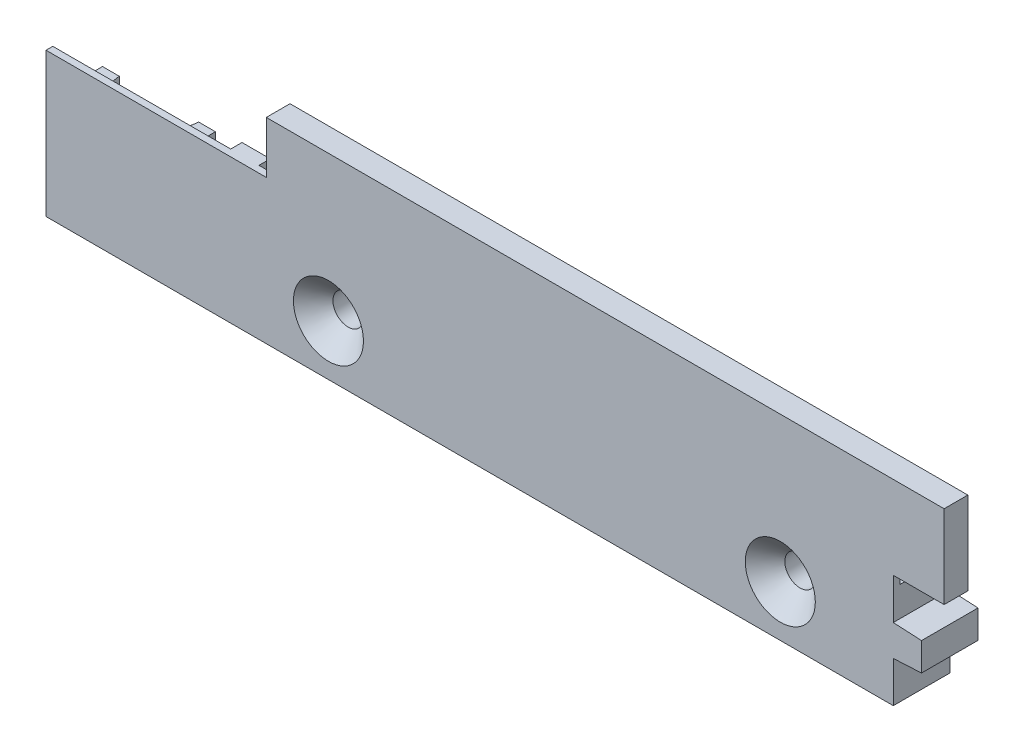
SolidWorks part; units mm, degrees
ref_plane "Front Plane" through (0, 0, 0) normal (0, 0, 1) x (1, 0, 0)
ref_plane "Top Plane" through (0, 0, 0) normal (0, 1, 0) x (1, 0, 0)
ref_plane "Right Plane" through (0, 0, 0) normal (1, 0, 0) x (0, 0, -1)
ref_axis "X-Axis" through (0, 0, 0) along (1, 0, 0)
ref_axis "Y-Axis" through (0, 42.2917, 0) along (0, -1, 0)
ref_axis "Z-Axis" through (0, 0, 55.0015) along (0, 0, -1)
sketch "Sketch1" plane through (0, 0, 0) normal (0, 0, 1) x (1, 0, 0)
  line L1 (-127.8191, -9.8629) -> (22.1809, -9.8629)
  line L2 (22.1809, -9.8629) -> (22.1809, -2.6129)
  line L3 (22.1809, -2.6129) -> (27.1809, -2.6129)
  line L4 (27.1809, -2.6129) -> (27.1809, 2.8871)
  line L5 (27.1809, 2.8871) -> (22.1809, 2.8871)
  line L6 (22.1809, 2.8871) -> (22.1809, 10.1371)
  line L7 (22.1809, 10.1371) -> (31.1809, 10.1371)
  line L8 (31.1809, 10.1371) -> (31.1809, 23.6371)
  line L10 (-127.8191, 15.6371) -> (-127.8191, -9.8629)
  line L12 (-88.8191, -25.8695) -> (-88.8191, 48.9262) construction
  line L13 (31.1809, 13.1371) -> (10.3885, 13.1371) construction
  line L14 (31.1809, 23.6371) -> (-88.8191, 23.6371) construction
  line L15 (-88.8191, 23.6371) -> (-88.8191, 15.6371)
  line L16 (-88.8191, 15.6371) -> (-127.8191, 15.6371)
  line L17 (31.1809, 23.6371) -> (31.1809, 24.8371)
  line L18 (31.1809, 24.8371) -> (-88.8191, 24.8371)
  line L19 (-88.8191, 24.8371) -> (-88.8191, 23.6371)
  point P5 (27.1809, 0.1371)
  dimension "D2" = 10
  dimension "D3" = 20
  dimension "D4" = 5.5
  dimension "D5" = 9
  dimension "D6" = 150
  dimension "D7" = 120
  dimension "D8" = 5
  dimension "D10" = 3
  dimension "D11" = 8
  dimension "D12" = 10.5
  dimension "D13" = 1.2
extrude "Boss-Extrude1" add sketch "Sketch1" along normal blind 10 and the other way blind 10
sketch "Sketch2" plane through (-127.8191, 0, 0) normal (-1, 0, 0) x (0, 0, 1)
  line L0 (-10, -9.8629) -> (10, -9.8629) construction
  line L1 (-8.8, 23.1371) -> (8.8, 23.1371) construction
  line L2 (-8.8, 23.1371) -> (-8.8, 8.1371)
  line L3 (-8.8, 8.1371) -> (8.8, 8.1371)
  line L4 (8.8, 23.1371) -> (8.8, 8.1371)
  line L5 (-10, 24.8371) -> (-10, 15.6371) construction
  line L7 (-10, 2.8871) -> (10, 2.8871) construction
  line L8 (-10, 15.6371) -> (-10, -9.8629) construction
  line L9 (10, 15.6371) -> (10, -9.8629) construction
  line L10 (0, 2.8871) -> (0, 23.1371) construction
  line L11 (-8.8, 23.1371) -> (-5.8, 23.1371)
  line L12 (-5.8, 23.1371) -> (-5.8, 24.8371)
  line L13 (-10, 24.8371) -> (10, 24.8371) construction
  line L14 (-5.8, 24.8371) -> (5.8, 24.8371)
  line L15 (5.8, 24.8371) -> (5.8, 23.1371)
  line L16 (5.8, 23.1371) -> (8.8, 23.1371)
  point P6 (0, 23.1371)
  dimension "D1" = 17.6
  dimension "D2" = 33
  dimension "D3" = 3
  dimension "D4" = 3
  dimension "D6" = 18
  dimension "D7" = 1.2
extrude "Cut-Extrude1" cut sketch "Sketch2" against normal offset from surface (157 mm away) 2 up to face at (31.1809, 17.4871, 0)
sketch "Sketch8" plane through (0, 0, 0) normal (0, 0, 1) x (1, 0, 0)
  line L0 (-127.8191, 15.6371) -> (-127.8191, -9.8629) construction
  line L1 (-107.8191, 24.8371) -> (17.1809, 24.8371)
  line L2 (-107.8191, 24.8371) -> (-107.8191, -9.8629)
  line L3 (-107.8191, -9.8629) -> (17.1809, -9.8629)
  line L4 (17.1809, 24.8371) -> (17.1809, -9.8629)
  line L5 (-127.8191, -9.8629) -> (22.1809, -9.8629) construction
  line L7 (22.1809, 2.8871) -> (22.1809, 10.1371) construction
  line L8 (29.1809, 24.8371) -> (-88.8191, 24.8371) construction
  point P12 (22.1809, 6.5121)
  dimension "D1" = 20
  dimension "D2" = 5
extrude "Cut-Extrude4" cut sketch "Sketch8" against normal blind 2.5 and the other way blind 2.5 contours L2 L3 L4 L1
sketch "Sketch9" plane through (0, 0, 0) normal (0, 0, 1) x (1, 0, 0)
  line L0 (-107.8191, -0.8629) -> (17.1809, -0.8629) construction
  line L1 (-107.8191, 8.1371) -> (-107.8191, -9.8629) construction
  line L2 (17.1809, 8.1371) -> (17.1809, -9.8629) construction
  circle A0 centre (-77.8191, -0.8629) radius 2.7
  circle A1 centre (2.1809, -0.8629) radius 2.7
  dimension "D1" = 5.4
  dimension "D2" = 80
  dimension "D3" = 15
extrude "Cut-Extrude5" cut sketch "Sketch9" against normal through all and the other way through all
chamfer "Chamfer2" distance 5 angle 3 2 edges at (27.1809, -2.6129, 0) (27.1809, 2.8871, 0) first distance on face at (24.6809, -2.6129, 0) first distance on face at (24.6809, 2.8871, 0)
sketch "Sketch14" plane through (0, 8.1371, 0) normal (0, 1, 0) x (1, 0, 0)
  line L0 (-120.3191, 4.5) -> (-115.3191, 4.5)
  line L1 (-115.3191, -4.5) -> (-120.3191, -4.5)
  line L2 (-107.8191, 0) -> (-127.8191, 0) construction
  line L3 (-107.8191, 2.5) -> (-107.8191, -2.5) construction
  line L5 (-127.8191, 8.8) -> (-127.8191, -8.8) construction
  arc A0 (-115.3191, 4.5) -> (-115.3191, -4.5) centre (-115.3191, 0) cw
  arc A1 (-120.3191, -4.5) -> (-120.3191, 4.5) centre (-120.3191, 0) cw
  point P16 (-117.8191, 0)
  dimension "D1" = 4.5
  dimension "D2" = 5
  dimension "D3" = 2.5
extrude "Cut-Extrude8" cut sketch "Sketch14" against normal blind 7
sketch "Sketch15" plane through (0, 1.1371, 0) normal (0, 1, 0) x (1, 0, 0)
  line L7 (-120.3191, -2.6) -> (-115.3191, -2.6)
  line L8 (-115.3191, 2.6) -> (-120.3191, 2.6)
  arc A2 (-120.3191, 4.5) -> (-120.3191, -4.5) centre (-120.3191, 0) ccw construction
  arc A3 (-115.3191, -4.5) -> (-115.3191, 4.5) centre (-115.3191, 0) ccw construction
  arc A6 (-120.3191, 2.6) -> (-120.3191, -2.6) centre (-120.3191, 0) ccw
  arc A7 (-115.3191, -2.6) -> (-115.3191, 2.6) centre (-115.3191, 0) ccw
  dimension "D2" = 2.6
extrude "Cut-Extrude9" cut sketch "Sketch15" against normal through all
sketch "Sketch16" plane through (0, 0, 0) normal (0, 0, 1) x (1, 0, 0)
  line L1 (-137.4451, 59.0989) -> (76.8996, 59.0989)
  line L2 (-137.4451, 59.0989) -> (-137.4451, -25.5467)
  line L3 (-137.4451, -25.5467) -> (76.8996, -25.5467)
  line L4 (76.8996, 59.0989) -> (76.8996, -25.5467)
extrude "Cut-Extrude10" cut sketch "Sketch16" against normal through all
sketch "Sketch17" plane through (0, 0, 0) normal (0, 0, -1) x (-1, 0, 0)
  line L1 (-31.1809, 24.8371) -> (-29.1809, 24.8371)
  line L2 (-31.1809, 24.8371) -> (-31.1809, 10.1371)
  line L3 (-31.1809, 10.1371) -> (-29.1809, 10.1371)
  line L4 (-29.1809, 24.8371) -> (-29.1809, 10.1371)
extrude "Cut-Extrude11" cut sketch "Sketch17" against normal up to surface (5.8 mm away) up to face at (-29.8191, 23.9871, 5.8)
sketch "Sketch18" plane through (0, 0, 0) normal (0, 0, -1) x (-1, 0, 0)
  line L0 (-27.1809, 0.1371) -> (-17.1809, 0.1371) construction
  line L1 (-27.1809, 2.6251) -> (-27.1809, -2.3509) construction
  line L2 (-17.1809, 8.1371) -> (-17.1809, -9.8629) construction
  line L3 (110.3191, -4.3629) -> (125.3191, -4.3629) construction
  line L5 (117.8191, -9.8629) -> (117.8191, 1.1371) construction
  line L9 (120.3191, 1.1371) -> (115.3191, 1.1371) construction
  line L10 (120.3191, -9.8629) -> (115.3191, -9.8629) construction
  circle A0 centre (110.3191, -4.3629) radius 1.35
  circle A1 centre (125.3191, -4.3629) radius 1.35
  circle A2 centre (-22.1809, 0.1371) radius 1.35
  point P17 (117.8191, -4.3629)
  dimension "D2" = 2.7
  dimension "D1" = 15
extrude "Cut-Extrude12" cut sketch "Sketch18" against normal blind 3
chamfer "Chamfer7" distance 3.5 angle 45 2 edges at (4.8809, -0.8629, 10) (-75.1191, -0.8629, 10)
sketch "Sketch19" plane through (0, 0, 8.8) normal (0, 0, -1) x (-1, 0, 0)
  line L0 (-22.1809, 8.1371) -> (127.8191, 8.1371) construction
  line L1 (91.3191, 15.6371) -> (96.3191, 15.6371)
  line L2 (91.3191, 15.6371) -> (91.3191, 8.1371)
  line L3 (91.3191, 8.1371) -> (96.3191, 8.1371)
  line L4 (96.3191, 15.6371) -> (96.3191, 8.1371)
  line L5 (-29.1809, 10.1371) -> (-29.1809, 23.1371) construction
  dimension "D1" = 120.5
  dimension "D2" = 5
extrude "Boss-Extrude2" add sketch "Sketch19" along normal blind 2
equation "\"Largeur Bande\"= 16.3"
equation "\"Largeur Feeder\"= \"Largeur Rail\" + 1.2 + 1.2 + 0.3"
equation "\"Largeur Rail\"= \"Largeur Bande\" + 1"
equation "\"D1@Boss-Extrude1\"=\"Largeur Feeder\"/2"
equation "\"D2@Boss-Extrude1\"=\"Largeur Feeder\"/2"
